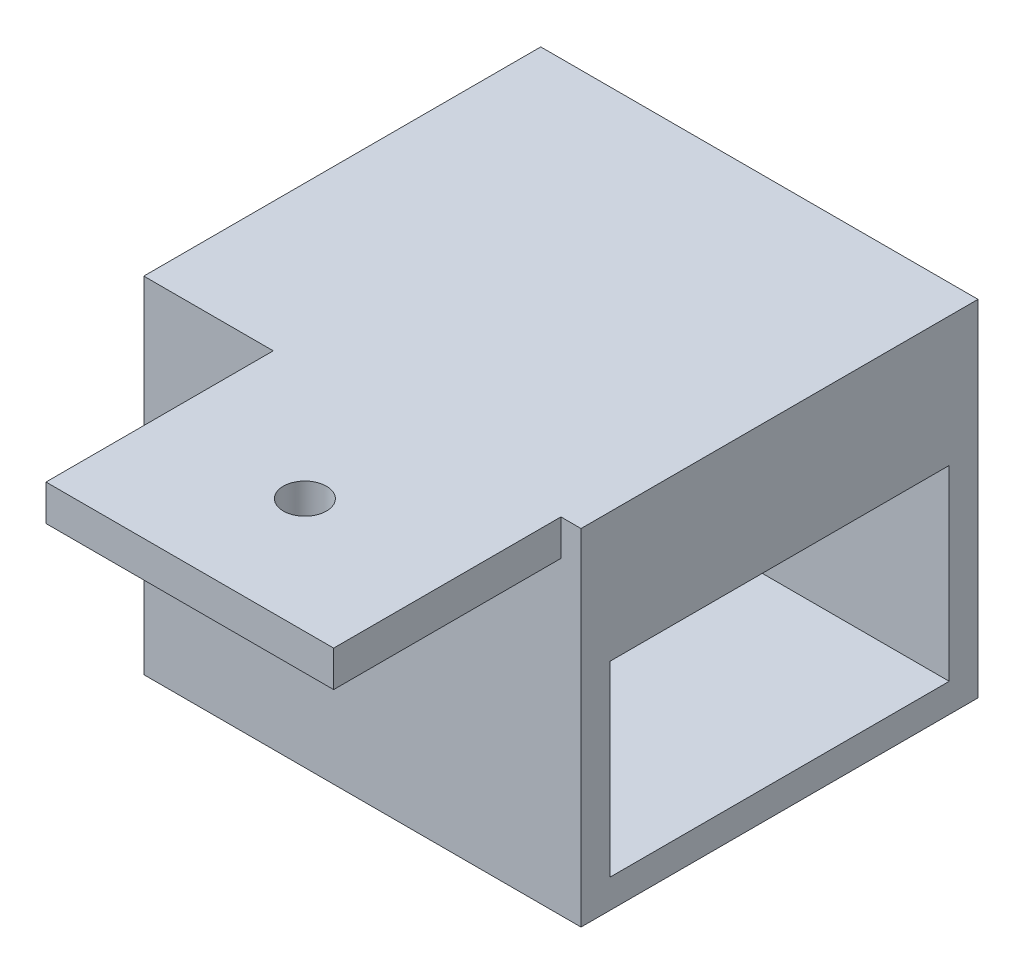
SolidWorks part; units mm, degrees
ref_plane "Front Plane" through (0, 0, 0) normal (0, 0, 1) x (1, 0, 0)
ref_plane "Top Plane" through (0, 0, 0) normal (0, 1, 0) x (1, 0, 0)
ref_plane "Right Plane" through (0, 0, 0) normal (1, 0, 0) x (0, 0, -1)
ref_plane "PZ_m34_000" through (0, 0, -34) normal (0, 0, 1) x (1, 0, 0)
sketch "S_box1" plane through (0, 0, -34) normal (0, 0, 1) x (1, 0, 0)
  line L0 (-10, -4) -> (10, -4)
  line L1 (10, -4) -> (10, -1.5)
  line L2 (10, -1.5) -> (-10, -1.5)
  line L3 (-10, -1.5) -> (-10, -4)
  dimension "P1" = 10
  dimension "P2" = 4
  dimension "P3" = 10
  dimension "P4" = 4
  dimension "P5" = 10
  dimension "P6" = 1.5
  dimension "P7" = 10
  dimension "P8" = 1.5
extrude "Boss_1" add sketch "S_box1" along normal blind 42
ref_plane "PZ_m35_400" through (0, 0, -35.4) normal (0, 0, 1) x (1, 0, 0)
sketch "S_box2" plane through (0, 0, -35.4) normal (0, 0, 1) x (1, 0, 0)
  line L0 (-19, -25.5) -> (11.4, -25.5)
  line L1 (11.4, -25.5) -> (11.4, -1.5)
  line L2 (11.4, -1.5) -> (-19, -1.5)
  line L3 (-19, -1.5) -> (-19, -25.5)
  dimension "P1" = 19
  dimension "P2" = 25.5
  dimension "P3" = 11.4
  dimension "P4" = 25.5
  dimension "P5" = 11.4
  dimension "P6" = 1.5
  dimension "P7" = 19
  dimension "P8" = 1.5
extrude "Boss_2" add sketch "S_box2" along normal blind 27.6
ref_plane "PZ_m33_400" through (0, 0, -33.4) normal (0, 0, 1) x (1, 0, 0)
sketch "S_cut3" plane through (0, 0, -33.4) normal (0, 0, 1) x (1, 0, 0)
  line L0 (-19.1, -23.5) -> (11.5, -23.5)
  line L1 (11.5, -23.5) -> (11.5, -10.5)
  line L2 (11.5, -10.5) -> (-19.1, -10.5)
  line L3 (-19.1, -10.5) -> (-19.1, -23.5)
  dimension "P1" = 19.1
  dimension "P2" = 23.5
  dimension "P3" = 11.5
  dimension "P4" = 23.5
  dimension "P5" = 11.5
  dimension "P6" = 10.5
  dimension "P7" = 19.1
  dimension "P8" = 10.5
extrude "Pocket_3" cut sketch "S_cut3" along normal blind 23.6
ref_plane "PZ_m35_500" through (0, 0, -35.5) normal (0, 0, 1) x (1, 0, 0)
sketch "S_cut4" plane through (0, 0, -35.5) normal (0, 0, 1) x (1, 0, 0)
  line L0 (-15, -8.5) -> (8, -8.5)
  line L1 (8, -8.5) -> (8, -4.5)
  line L2 (8, -4.5) -> (-15, -4.5)
  line L3 (-15, -4.5) -> (-15, -8.5)
  dimension "P1" = 15
  dimension "P2" = 8.5
  dimension "P3" = 8
  dimension "P4" = 8.5
  dimension "P5" = 8
  dimension "P6" = 4.5
  dimension "P7" = 15
  dimension "P8" = 4.5
extrude "Pocket_4" cut sketch "S_cut4" along normal blind 23.7
ref_plane "PY_m4_100" through (0, -4.1, 0) normal (0, 1, 0) x (1, 0, 0)
sketch "S_hole5" plane through (0, -4.1, 0) normal (0, 1, 0) x (1, 0, 0)
  circle A0 centre (0, 0) radius 1.5
  dimension "D1_S_hole5" = 3
extrude "Hole_5" cut sketch "S_hole5" along normal blind 2.7
equation "\"plate_t\" = 3"
equation "\"clearance\" = 0.4"
